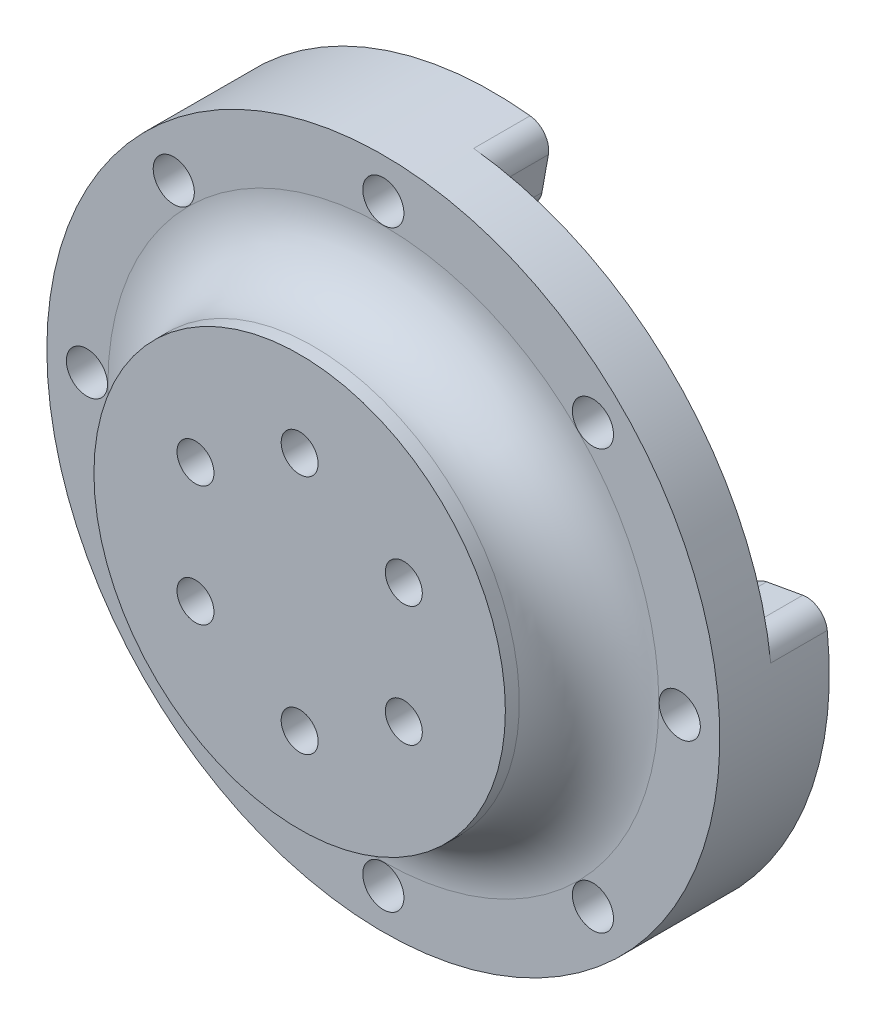
SolidWorks part; units mm, degrees
note: '?' marks a value the reader was unsure of.
ref_plane "前视基准面" through (0, 0, 0) normal (0, 0, 1) x (1, 0, 0)
ref_plane "上视基准面" through (0, 0, 0) normal (0, 1, 0) x (1, 0, 0)
ref_plane "右视基准面" through (0, 0, 0) normal (1, 0, 0) x (0, 0, -1)
other "Configuration Table"
sketch "草图1" plane through (0, 0, 0) normal (0, 0, 1) x (1, 0, 0)
  line L0 (0, 35.7035) -> (0, -37.1802) construction
  circle A1 centre (0, 0) radius 17.25 construction
  circle A2 centre (0, 17.25) radius 1.65
  circle A3 centre (14.9389, 8.625) radius 1.65
  circle A4 centre (14.9389, -8.625) radius 1.65
  circle A5 centre (0, -17.25) radius 1.65
  circle A6 centre (-14.9389, -8.625) radius 1.65
  circle A7 centre (-14.9389, 8.625) radius 1.65
  circle A29 centre (0, 0) radius 29.5
  point P20 (0, 0)
  point P37 (0, 0)
  point P54 (0, 0)
  dimension "D2" = 34.5
  dimension "D3" = 3.3
  dimension "D10" = 59
  dimension "D4" = 6
extrude "凸台-拉伸1" add sketch "草图1" along normal blind 12
sketch "草图3" plane through (0, 0, 0) normal (0, 0, -1) x (-1, 0, 0)
  line L0 (0, 53.342) -> (0, -54.174) construction
  line L1 (0, 0) -> (30.052, 30.052) construction
  line L2 (0, 0) -> (42.5, 0) construction
  line L3 (0, 0) -> (30.052, -30.052) construction
  line L4 (-30.052, 30.052) -> (0, 0) construction
  line L5 (0, 0) -> (-42.5, 0) construction
  line L6 (0, 0) -> (-30.052, -30.052) construction
  circle A0 centre (0, 0) radius 27
  circle A1 centre (0, 0) radius 37.5 construction
  arc A19 (-31.7103, 36.3665) -> (-36.3665, -31.7103) centre (0, 0) ccw
  arc A20 (-31.7103, -36.3665) -> (0, -48.25) centre (0, 0) ccw
  arc A21 (36.3665, -31.7103) -> (36.3665, 31.7103) centre (0, 0) ccw
  arc A22 (0, -48.25) -> (31.7103, -36.3665) centre (0, 0) ccw
  arc A23 (31.7103, 36.3665) -> (-31.7103, 36.3665) centre (0, 0) ccw
  circle A24 centre (30.052, 30.052) radius 1.8
  circle A25 centre (42.5, 0) radius 1.8
  circle A26 centre (30.052, -30.052) radius 1.8
  circle A27 centre (0, -42.5) radius 1.8
  circle A28 centre (0, 0) radius 42.5 construction
  circle A29 centre (0, 42.5) radius 1.8
  circle A32 centre (-30.052, -30.052) radius 1.8
  circle A33 centre (-42.5, 0) radius 1.8
  circle A34 centre (0, 0) radius 48.25
  circle A35 centre (-30.052, 30.052) radius 1.8
  point P24 (0, 0)
  point P32 (0, 0)
  point P40 (0, 0)
  dimension "D1" = 54
  dimension "D2" = 75
  dimension "D3" = 3.6
  dimension "D5" = 45
  dimension "D7" = 96.5
  dimension "D8" = 85
  dimension "D4" = 45
  dimension "D6" = 45
  dimension "D9" = 45
  dimension "D10" = 45
  dimension "D11" = 45
extrude "凸台-拉伸2" add sketch "草图3" along normal blind 7.6 separate body
sketch "草图4" plane through (0, 0, 0) normal (0, 0, -1) x (-1, 0, 0)
  circle A0 centre (0, 0) radius 31.6888
  circle A1 centre (0, 17.25) radius 1.65
  circle A2 centre (14.9389, 8.625) radius 1.65
  circle A3 centre (14.9389, -8.625) radius 1.65
  circle A4 centre (0, -17.25) radius 1.65
  circle A5 centre (-14.9389, -8.625) radius 1.65
  circle A6 centre (-14.9389, 8.625) radius 1.65
  point P18 (0, 0)
  dimension "D1" = 6
extrude "凸台-拉伸3" add sketch "草图4" along normal up to surface (7.6 mm away) up to face at (-27, 0, -7.6)
hole_wizard "M4.5 开槽半沉头木螺钉的锥形沉头孔1" positions "草图5" profile "草图6" countersink size "M4.5" standard "GB"
sketch "草图5" plane through (0, 0, -7.6) normal (0, 0, -1) x (-1, 0, 0)
  point P0 (0, 17.25)
  point P3 (-14.9389, 8.625)
  point P6 (-14.9389, -8.625)
  point P9 (0, -17.25)
  point P12 (14.9389, -8.625)
  point P15 (14.9389, 8.625)
sketch "草图6" plane through (0, 17.25, -7.6) normal (1, 0, 0) x (0, 1, 0)
  line L0 (0, 0) -> (0, 101.5923)
  line L1 (0, 101.5923) -> (2.65, 100)
  line L2 (2.65, 100) -> (2.65, 2.4)
  line L3 (2.65, 2.4) -> (5.05, 0)
  line L5 (5.05, 0) -> (0, 0)
  line L6 (-2.65, 2.4) -> (-5.05, 0) construction
  line L10 (0, 101.5923) -> (-2.65, 100) construction
  line L11 (0, -6.35) -> (0, 107.95) construction
  dimension "孔直径" = 5.3
  dimension "孔深度" = 100
  dimension "近端锥形沉头孔直径" = 10.1
  dimension "近端锥形沉头孔角度" = 90
  dimension "导头角度" = 118
sketch "草图7" plane through (0, 0, -7.6) normal (0, 0, -1) x (-1, 0, 0)
  line L2 (-7.0389, 39.2613) -> (-7.9677, 44.4418)
  line L3 (39.2711, -7.0477) -> (44.4536, -7.958)
  line L4 (-30.052, 30.052) -> (30.052, -30.052) construction
  line L5 (7.0477, -39.2711) -> (7.958, -44.4536)
  line L6 (-39.2613, 7.0389) -> (-44.4418, 7.9677)
  circle A2 centre (0, 42.5) radius 1.8 construction
  circle A4 centre (0, -42.5) radius 1.8
  circle A5 centre (42.5, 0) radius 1.8 construction
  arc A8 (47.9542, -5.3349) -> (-5.3473, 47.9528) centre (0, 0) ccw
  arc A9 (36.8058, -3.7859) -> (-3.7796, 36.8065) centre (0, 0) ccw
  arc A10 (-7.9677, 44.4418) -> (-5.3473, 47.9528) centre (-5.0148, 44.9713) cw
  arc A11 (-3.7796, 36.8065) -> (-7.0389, 39.2613) centre (-4.086, 39.7908) cw
  arc A12 (44.4536, -7.958) -> (47.9542, -5.3349) centre (44.9726, -5.0032) ccw
  arc A13 (39.2711, -7.0477) -> (36.8058, -3.7859) centre (39.7901, -4.0929) cw
  circle A18 centre (0, 42.5) radius 1.8
  circle A19 centre (30.052, 30.052) radius 1.8
  circle A20 centre (42.5, 0) radius 1.8
  circle A24 centre (-30.052, -30.052) radius 1.8
  circle A25 centre (-42.5, 0) radius 1.8
  arc A26 (7.0477, -39.2711) -> (3.7859, -36.8058) centre (4.0929, -39.7901) ccw
  arc A27 (7.958, -44.4536) -> (5.3349, -47.9542) centre (5.0032, -44.9726) cw
  arc A28 (5.3349, -47.9542) -> (-47.9528, 5.3473) centre (0, 0) cw
  arc A29 (-44.4418, 7.9677) -> (-47.9528, 5.3473) centre (-44.9713, 5.0148) ccw
  arc A30 (-36.8065, 3.7796) -> (-39.2613, 7.0389) centre (-39.7908, 4.086) ccw
  arc A31 (3.7859, -36.8058) -> (-36.8065, 3.7796) centre (0, 0) cw
  point P24 (47.4967, -8.4925)
  point P27 (36.4163, -6.5462)
  dimension "D1" = 3.6
  dimension "D5" = 3.6
  dimension "D6" = 3
  dimension "D4" = 3.6
  dimension "D2" = 7.5
  dimension "D3" = 7.5
extrude "凸台-拉伸4" add sketch "草图7" along normal blind 8.1
ref_axis "基准轴1" through (0, 42.5, -15.7) along (0, 0, 1)?
ref_axis "基准轴2" through (-42.5, 0, -15.7) along (0, 0, 1)?
ref_plane "基准面1" through (-20.4765, -21.2359, 0) normal (-0.6941, -0.7199, 0) x (0, 0, 1)
sketch "草图8" plane through (-20.4765, -21.2359, 0) normal (-0.6941, -0.7199, 0) x (0, 0, 1)
  line L0 (0, 28.7941) -> (0, 32.3941) construction
  line L1 (0, 28.7941) -> (0, 32.3941)
  line L2 (0, 30.5941) -> (0, 33.5441)
  line L3 (0, 33.5441) -> (-7.7, 33.5441)
  line L4 (-7.7, 33.5441) -> (-7.7, 30.5941)
  line L5 (0, 30.5941) -> (-7.7, 30.5941)
  dimension "D1" = 2.95
  dimension "D2" = 2.95
  dimension "D3" = 7.7
revolve "切除-旋转1" cut sketch "草图8" angle 360 about L5
sketch "草图10" plane through (0, 0, 0) normal (0, 0, 1) x (1, 0, 0)
  circle A0 centre (-30.052, 30.052) radius 1.8 construction
  circle A1 centre (-30.052, 30.052) radius 1.8
  circle A2 centre (42.5, 0) radius 1.8 construction
  circle A3 centre (30.052, -30.052) radius 1.8 construction
  circle A4 centre (0, -42.5) radius 1.8 construction
  circle A5 centre (30.052, 30.052) radius 1.8 construction
  circle A6 centre (0, 42.5) radius 1.8 construction
  circle A7 centre (42.5, 0) radius 1.8
  circle A8 centre (30.052, -30.052) radius 1.8
  circle A9 centre (0, -42.5) radius 1.8
  circle A10 centre (30.052, 30.052) radius 1.8
  circle A11 centre (0, 42.5) radius 1.8
extrude "切除-拉伸1" cut sketch "草图10" against normal blind 82
fillet "圆角1" radius 10 1 edges at (29.5, 0, 0)
pattern_circular "阵列(圆周)1" count 8 every 45 about axis through (0, 0, 0) along (0, 0, 1) of "切除-旋转1"
sketch "草图11" plane through (0, 0, -15.7) normal (0, 0, -1) x (-1, 0, 0)
  line L2 (-7.9677, 44.4418) -> (-7.0389, 39.2613)
  line L3 (39.2711, -7.0477) -> (44.4536, -7.958)
  line L4 (-7.9677, 44.4418) -> (-7.0389, 39.2613)
  line L5 (39.2711, -7.0477) -> (44.4536, -7.958)
  circle A0 centre (42.5, 0) radius 1.8 construction
  circle A1 centre (30.052, 30.052) radius 1.8 construction
  circle A2 centre (0, 42.5) radius 1.8 construction
  circle A3 centre (42.5, 0) radius 1.8
  circle A4 centre (30.052, 30.052) radius 1.8
  circle A5 centre (0, 42.5) radius 1.8
  arc A6 (-7.0389, 39.2613) -> (-3.7796, 36.8065) centre (-4.086, 39.7908) ccw
  arc A7 (36.8058, -3.7859) -> (-3.7796, 36.8065) centre (0, 0) ccw
  arc A8 (36.8058, -3.7859) -> (39.2711, -7.0477) centre (39.7901, -4.0929) ccw
  arc A9 (44.4536, -7.958) -> (47.9542, -5.3349) centre (44.9726, -5.0032) ccw
  arc A10 (47.9542, -5.3349) -> (-5.3473, 47.9528) centre (0, 0) ccw
  arc A11 (-5.3473, 47.9528) -> (-7.9677, 44.4418) centre (-5.0148, 44.9713) ccw
  arc A12 (-7.0389, 39.2613) -> (-3.7796, 36.8065) centre (-4.086, 39.7908) ccw
  arc A13 (36.8058, -3.7859) -> (-3.7796, 36.8065) centre (0, 0) ccw
  arc A14 (36.8058, -3.7859) -> (39.2711, -7.0477) centre (39.7901, -4.0929) ccw
  arc A15 (44.4536, -7.958) -> (47.9542, -5.3349) centre (44.9726, -5.0032) ccw
  arc A16 (47.9542, -5.3349) -> (-5.3473, 47.9528) centre (0, 0) ccw
  arc A17 (-5.3473, 47.9528) -> (-7.9677, 44.4418) centre (-5.0148, 44.9713) ccw
  dimension "D1" = 0
